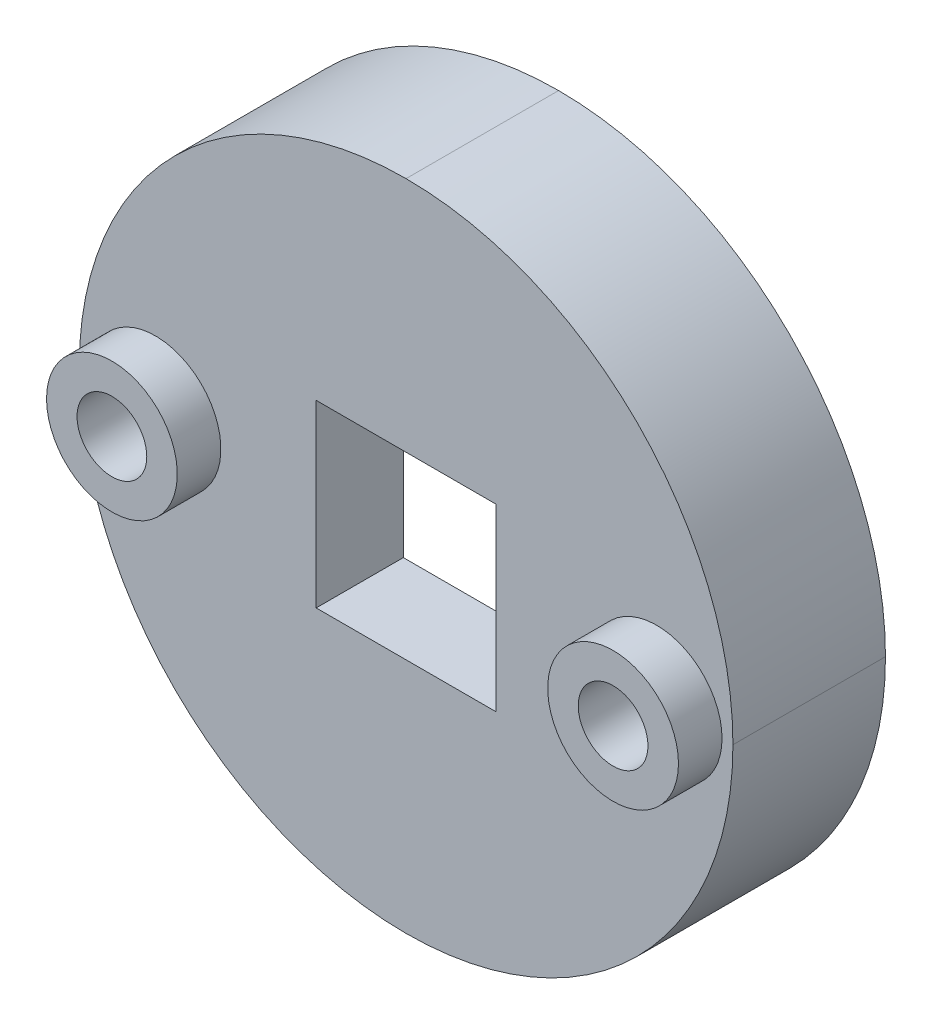
SolidWorks part; units mm, degrees
ref_plane "Спереди" through (0, 0, 0) normal (0, 0, 1) x (1, 0, 0)
ref_plane "Сверху" through (0, 0, 0) normal (0, 1, 0) x (1, 0, 0)
ref_plane "Справа" through (0, 0, 0) normal (1, 0, 0) x (0, 0, -1)
sketch "Эскиз1" plane through (0, 0, 0) normal (0, 0, 1) x (1, 0, 0)
  line L1 (-15, 15) -> (15, 15)
  line L2 (-15, 15) -> (-15, -15)
  line L3 (-15, -15) -> (15, -15)
  line L4 (15, 15) -> (15, -15)
  line L5 (-15, 15) -> (15, -15) construction
  line L6 (-15, -15) -> (15, 15) construction
  point P0 (0, 0)
  dimension "D1" = 30
  dimension "D2" = 30
extrude "Бобышка-Вытянуть1" add sketch "Эскиз1" along normal blind 7
sketch "Эскиз2" plane through (0, 0, 7) normal (0, 0, 1) x (1, 0, 0)
  line L1 (-4.125, 4.125) -> (4.125, 4.125)
  line L2 (-4.125, 4.125) -> (-4.125, -4.125)
  line L3 (-4.125, -4.125) -> (4.125, -4.125)
  line L4 (4.125, 4.125) -> (4.125, -4.125)
  line L5 (-4.125, 4.125) -> (4.125, -4.125) construction
  line L6 (-4.125, -4.125) -> (4.125, 4.125) construction
  point P0 (0, 0)
  dimension "D1" = 8.25
  dimension "D2" = 8.25
extrude "Вырез-Вытянуть1" cut sketch "Эскиз2" against normal through all
sketch "Эскиз3" plane through (0, 0, 7) normal (0, 0, 1) x (1, 0, 0)
  line L0 (-13.8303, 0) -> (13.8303, 0) construction
  line L1 (0, -11.3506) -> (0, 12.4019) construction
  circle A0 centre (11.5, 0) radius 3
  circle A1 centre (-11.5, 0) radius 3
  point P5 (0, 0)
  dimension "D1" = 6
  dimension "D2" = 11.5
extrude "Бобышка-Вытянуть2" add sketch "Эскиз3" along normal blind 2
sketch "Эскиз4" plane through (0, 0, 9) normal (0, 0, 1) x (1, 0, 0)
  circle A0 centre (-11.5, 0) radius 1.6
  circle A1 centre (11.5, 0) radius 1.6
  dimension "D1" = 3.2
extrude "Вырез-Вытянуть2" cut sketch "Эскиз4" against normal blind 5
sketch "Эскиз5" plane through (0, 0, 0) normal (0, 0, -1) x (-1, 0, 0)
  circle A0 centre (0, 0) radius 12.625
  dimension "D1" = 25.25
extrude "Вырез-Вытянуть3" cut sketch "Эскиз5" against normal blind 3
fillet "Скругление1" radius 15 4 edges at (-15, 15, 3.5) (15, 15, 3.5) (15, -15, 3.5) (-15, -15, 3.5)
